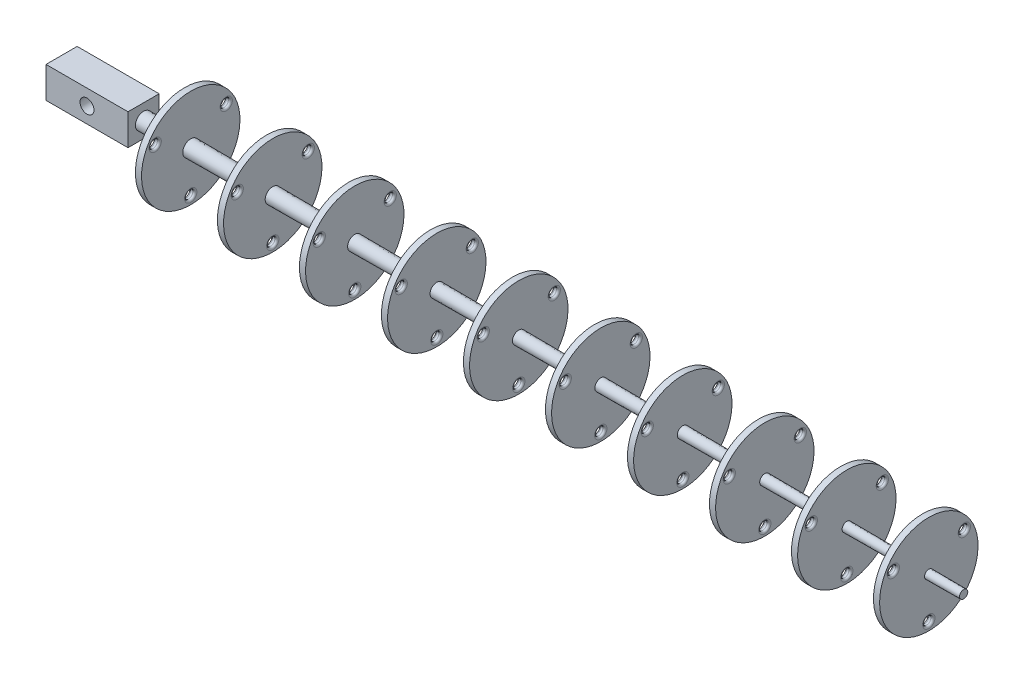
SolidWorks part; units mm, degrees
ref_plane "Front Plane" through (0, 0, 0) normal (0, 0, 1) x (1, 0, 0)
ref_plane "Top Plane" through (0, 0, 0) normal (0, 1, 0) x (1, 0, 0)
ref_plane "Right Plane" through (0, 0, 0) normal (1, 0, 0) x (0, 0, -1)
sketch "Sketch2" plane through (0, 0, 0) normal (0, 0, 1) x (1, 0, 0)
  line L0 (0, 2) -> (200, 1)
  line L1 (0, -13.2) -> (0, 13.2) construction
  line L2 (200, 1) -> (200, 0)
  line L3 (200, 0) -> (0, 0)
  line L4 (0, 0) -> (0, 2)
  dimension "D1" = 2
  dimension "D2" = 200
  dimension "D3" = 1
revolve "Revolve1" add sketch "Sketch2" angle 360 about L3
ref_axis "Axis1" through (-3.9062, 0, 0) along (1, 0, 0)
sketch "Sketch3" plane through (0, 0, 0) normal (0, 0, 1) x (1, 0, 0)
  line L0 (10, 0) -> (10, 12)
  line L1 (10, 12) -> (11.5, 12)
  line L2 (11.5, 12) -> (11.5, 0)
  line L3 (11.5, 0) -> (10, 0)
  line L4 (0, -15.4) -> (0, 15.4) construction
  dimension "D1" = 1.5
  dimension "D2" = 12
  dimension "D3" = 10
revolve "Revolve2" add sketch "Sketch3" angle 360 about L3
sketch "Sketch5" plane through (11.5, 0, 0) normal (1, 0, 0) x (0, 0, -1)
  line L0 (0, -10) -> (0, 0) construction
  line L1 (0, 0) -> (8.6603, 5) construction
  line L2 (-8.6603, 5) -> (0, 0) construction
  line L3 (0, 13.2) -> (0, -13.2) construction
  circle A0 centre (0, -10) radius 1
  circle A1 centre (8.6603, 5) radius 1
  circle A2 centre (-8.6603, 5) radius 1
  dimension "D2" = 2
  dimension "D1" = 10
  dimension "D3" = 120
  dimension "D4" = 120
extrude "Cut-Extrude1" cut sketch "Sketch5" against normal up to next
fillet "Fillet1" radius 0.5 6 edges at (10, 4, -8.6603) (10, -11, 0) (11.5, -9, 0) (11.5, 6, -8.6603) (10, 4, 8.6603) (11.5, 6, 8.6603)
pattern_linear "LPattern1" count 10 spacing 20 along (1, 0, 0) of "Revolve2", "Cut-Extrude1", "Fillet1"
sketch "Sketch16" plane through (0, 0, 0) normal (-1, 0, 0) x (0, 0, 1)
  line L1 (-3.8, -3.8) -> (3.8, -3.8)
  line L2 (-3.8, -3.8) -> (-3.8, 3.8)
  line L3 (-3.8, 3.8) -> (3.8, 3.8)
  line L4 (3.8, -3.8) -> (3.8, 3.8)
  line L5 (-3.8, -3.8) -> (3.8, 3.8) construction
  line L6 (-3.8, 3.8) -> (3.8, -3.8) construction
  point P0 (0, 0)
  dimension "D1" = 7.6
extrude "Boss-Extrude1" add sketch "Sketch16" along normal blind 20
sketch "Sketch19" plane through (0, 0, -3.8) normal (0, 0, -1) x (-1, 0, 0)
  line L0 (3.9062, 0) -> (-200, 0) construction
  line L1 (20, 3.8) -> (0, 3.8) construction
  line L2 (20, 3.8) -> (20, -3.8) construction
  point P0 (10, 0)
  point P7 (10, 3.8)
  point P10 (20, 0)
hole_wizard "M3 Clearance Hole1" positions "Sketch19" profile "Sketch18" hole size "M3" standard "ANSI Metric" end condition through all
sketch "Sketch18" plane through (-10, 0, -3.8) normal (1, 0, 0) x (0, 1, 0)
  line L0 (0, 0) -> (0, 15.8)
  line L1 (0, 15.8) -> (1.7, 15.8)
  line L2 (1.7, 15.8) -> (1.7, 0.025)
  line L3 (1.7, 0.025) -> (1.725, 0)
  line L5 (1.725, 0) -> (0, 0)
  line L6 (-1.7, 0.025) -> (-1.725, 0) construction
  line L11 (0, -6.35) -> (0, 107.95) construction
  dimension "Thru Hole Dia." = 3.4
  dimension "Thru Hole Depth" = 15.8
  dimension "Near C'Sink Dia." = 3.45
  dimension "Near C'Sink Angle" = 90
equation "\"R_initial\"= 2"
equation "\"D1@Sketch2\"=\"R_initial\""
equation "\"R_distal\"= 1"
equation "\"D3@Sketch2\"=\"R_distal\""
equation "\"L\"=200"
equation "\"D2@Sketch2\"=\"L\""
equation "\"disk_thickness\"= 1.5"
equation "\"D1@Sketch3\"=\"disk_thickness\""
equation "\"disk_radius\"= 12"
equation "\"D2@Sketch3\"=\"disk_radius\""
equation "\"disk_spacing_initial\"= 10"
equation "\"D3@Sketch3\"=\"disk_spacing_initial\""
equation "\"tendon_routing_radius\"= 10"
equation "\"D1@Sketch5\"=\"tendon_routing_radius\""
equation "\"tendon_routing_hole_radius\"=2"
equation "\"D2@Sketch5\"=\"tendon_routing_hole_radius\""
equation "\"tendon_routing_hole_fillet\"=0.5"
equation "\"D1@Fillet1\"=\"tendon_routing_hole_fillet\""
equation "\"inter_disk_spacing\"= 20"
equation "\"D3@LPattern1\"=\"inter_disk_spacing\""
equation "\"num_disk\"= 10"
equation "\"D1@LPattern1\"=\"num_disk\""
